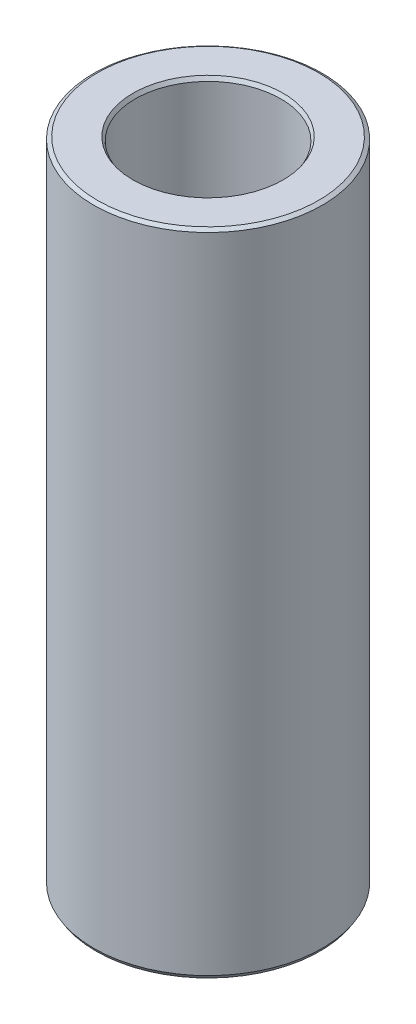
SolidWorks part; units mm, degrees
ref_plane "Front Plane" through (0, 0, 0) normal (0, 0, 1) x (1, 0, 0)
ref_plane "Top Plane" through (0, 0, 0) normal (0, 1, 0) x (1, 0, 0)
ref_plane "Right Plane" through (0, 0, 0) normal (1, 0, 0) x (0, 0, -1)
sketch "Sketch1" plane through (0, 0, 0) normal (0, 1, 0) x (1, 0, 0)
  circle A0 centre (0, 0) radius 22.5
  dimension "SLEEVE_OD" = 45
extrude "Boss-Extrude1" add sketch "Sketch1" along normal blind 127.8894
sketch "Sketch2" plane through (0, 0, 0) normal (0, 1, 0) x (1, 0, 0)
  circle A0 centre (0, 0) radius 14.3322
  dimension "BORE_D" = 28.6644
extrude "Cut-Extrude1" cut sketch "Sketch2" along normal through all
chamfer "Chamfer1" distance 0.4582 angle 57.864 4 edges at (0, 127.8894, 14.3322) (0, 0, 14.3322) (0, 0, 22.5) (0, 127.8894, 22.5) first distance on face at (0, 127.8894, 14.3322) first distance on face at (0, 0, 14.3322) first distance on face at (0, 127.8894, 22.5)
